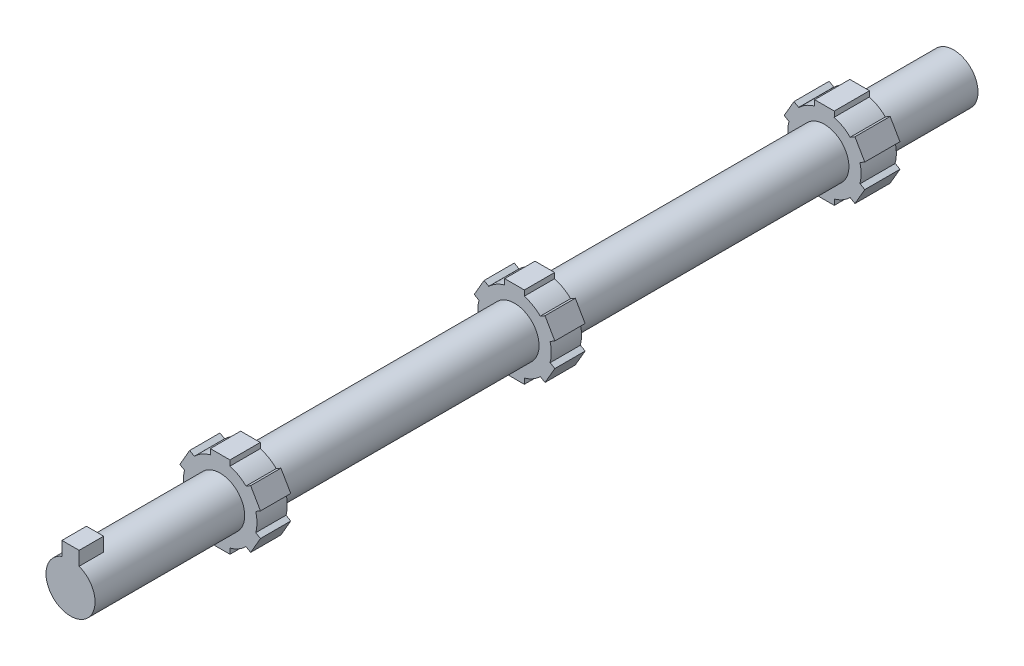
SolidWorks part; units mm, degrees
ref_plane "Front Plane" through (0, 0, 0) normal (0, 0, 1) x (1, 0, 0)
ref_plane "Top Plane" through (0, 0, 0) normal (0, 1, 0) x (1, 0, 0)
ref_plane "Right Plane" through (0, 0, 0) normal (1, 0, 0) x (0, 0, -1)
sketch "Sketch3" plane through (0, 0, 0) normal (1, 0, 0) x (0, 0, -1)
  line L0 (-207, 11.5) -> (-136.85, 11.5)
  line L1 (-136.85, 11.5) -> (-136.85, 17.25)
  line L2 (-136.85, 17.25) -> (-122.65, 17.25)
  line L3 (-122.65, 17.25) -> (-122.65, 11.5)
  line L4 (-122.65, 11.5) -> (1.15, 11.5)
  line L5 (1.15, 11.5) -> (1.15, 17.2186)
  line L6 (1.15, 17.2186) -> (15.35, 17.2186)
  line L7 (15.35, 17.2186) -> (15.35, 11.4686)
  line L8 (15.35, 11.4686) -> (146.45, 11.4686)
  line L9 (146.45, 11.4686) -> (146.45, 17.1872)
  line L10 (146.45, 17.1872) -> (162.95, 17.1872)
  line L11 (162.95, 17.1872) -> (162.95, 11.4372)
  line L12 (162.95, 11.4372) -> (207, 11.4372)
  line L13 (207, 11.4372) -> (207, 0)
  line L14 (207, 0) -> (-207, 0)
  line L15 (-207, 0) -> (-207, 11.5)
  dimension "D1" = 11.5
  dimension "D2" = 70.15
  dimension "D3" = 14.2
  dimension "D4" = 414
  dimension "D5" = 131.1
  dimension "D6" = 14.2
  dimension "D7" = 16.5
  dimension "D8" = 123.8
  dimension "D9" = 207
  dimension "D10" = 5.75
  dimension "D11" = 5.75
  dimension "D12" = 5.75
revolve "Revolve1" add sketch "Sketch3" angle 360 about L14
sketch "Sketch4" plane through (0, 0, 0) normal (0, 0, 1) x (1, 0, 0)
  line L1 (4.6, 19.16) -> (-4.6, 19.16)
  line L2 (4.6, 19.16) -> (4.6, 16.63)
  line L3 (4.6, 16.63) -> (-4.6, 16.63)
  line L4 (-4.6, 19.16) -> (-4.6, 16.63)
  circle A0 centre (0, 0) radius 17.25 construction
  point P0 (0, 17.25)
  point P7 (0, 0)
  dimension "D1" = 9.2
  dimension "D2" = 2.53
  dimension "D3" = 16.63
extrude "Boss-Extrude2" add sketch "Sketch4" against normal up to surface (-122.65 mm away) from surface up to face at (0, 17.25, 122.65) starting at face at (0, 11.5, 136.85)
extrude "Boss-Extrude3" add sketch "Sketch4<2>" along direction (0, 0, -1) on the side against the normal up to surface (15.35 mm away) from surface up to face at (0, 17.2186, -15.35) starting at face at (0, 11.5, -1.15)
sketch "Sketch4<2>" plane through (0, 0, 0) normal (0, 0, 1) x (1, 0, 0) same geometry as "Sketch4"
extrude "Boss-Extrude4" add sketch "Sketch4<3>" against normal up to surface (162.95 mm away) from surface up to face at (0, 17.1872, -162.95) starting at face at (0, 11.4686, -146.45)
sketch "Sketch4<3>" plane through (0, 0, 0) normal (0, 0, 1) x (1, 0, 0) same geometry as "Sketch4"
pattern_circular "CirPattern1" count 6 over 360 about axis through (0, 0, -207) along (0, 0, -1) of "Boss-Extrude3"
pattern_circular "CirPattern2" count 6 over 360 about axis through (0, 0, -207) along (0, 0, -1) of "Boss-Extrude2" reverse direction yes
pattern_circular "CirPattern3" count 6 over 360 about axis through (0, 0, -207) along (0, 0, -1) of "Boss-Extrude4" reverse direction yes
sketch "Sketch5" plane through (0, 0, 0) normal (0, 0, 1) x (1, 0, 0)
  line L1 (4.0321, 17.25) -> (-4.0321, 17.25)
  line L2 (4.0321, 17.25) -> (4.0321, 5.75)
  line L3 (4.0321, 5.75) -> (-4.0321, 5.75)
  line L4 (-4.0321, 17.25) -> (-4.0321, 5.75)
  line L5 (4.0321, 17.25) -> (-4.0321, 5.75) construction
  line L6 (4.0321, 5.75) -> (-4.0321, 17.25) construction
  circle A0 centre (0, 0) radius 11.5 construction
  circle A1 centre (0, 0) radius 11.5 construction
  point P0 (0, 11.5)
  dimension "D1" = 11.5
extrude "Boss-Extrude5" add sketch "Sketch5" against normal blind 11.5 from surface starting at face at (0, 11.5, 207)
